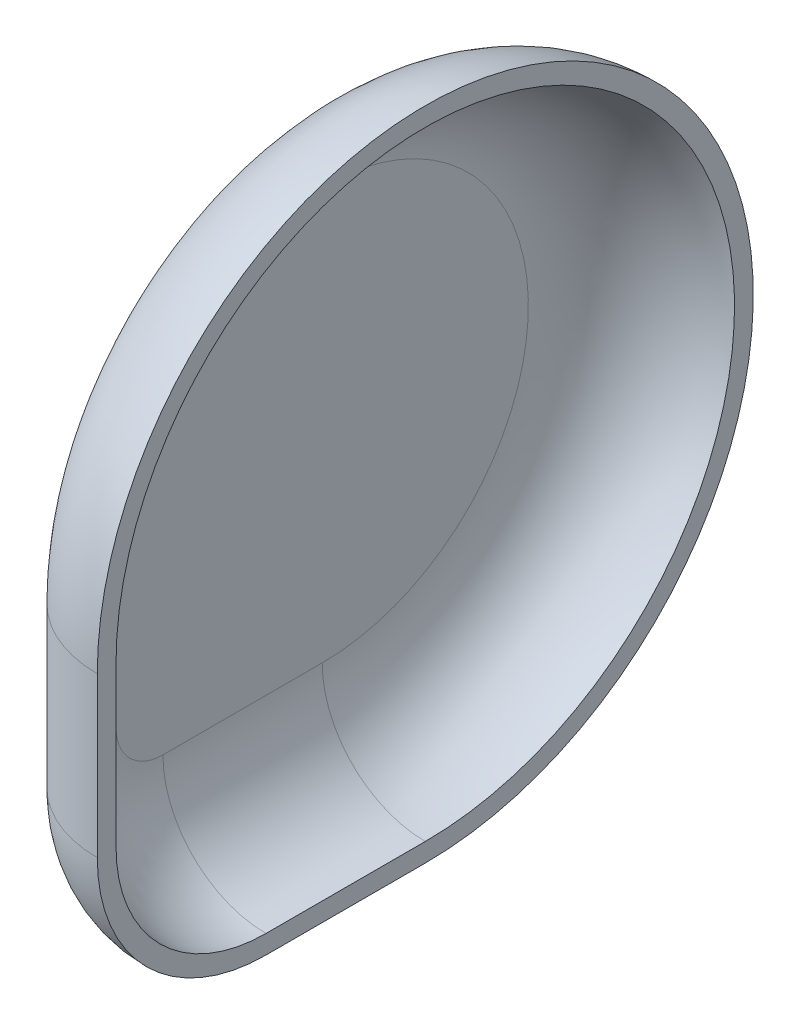
SolidWorks part; units mm, degrees
ref_plane "Alzado" through (0, 0, 0) normal (0, 0, 1) x (1, 0, 0)
ref_plane "Planta" through (0, 0, 0) normal (0, 1, 0) x (1, 0, 0)
ref_plane "Vista lateral" through (0, 0, 0) normal (1, 0, 0) x (0, 0, -1)
sketch "Croquis1" plane through (0, 0, 0) normal (1, 0, 0) x (0, 0, -1)
  line L0 (0, -35) -> (-17, -35)
  line L1 (-35, -17) -> (-35, 0)
  arc A0 (0, -35) -> (-35, 0) centre (0, 0) ccw
  arc A1 (-35, -17) -> (-17, -35) centre (-17, -17) ccw
  dimension "D1" = 18
extrude "Saliente-Extruir1" add sketch "Croquis1" along normal blind 13
fillet "Redondeo1" radius 13 4 edges at (0, -35, 8.5) (0, -29.7279, 29.7279) (0, -8.5, 35) (0, 24.7487, -24.7487)
shell "Vaciado1" thickness 2 removed face at (13, -12.1198, 12.1198)
